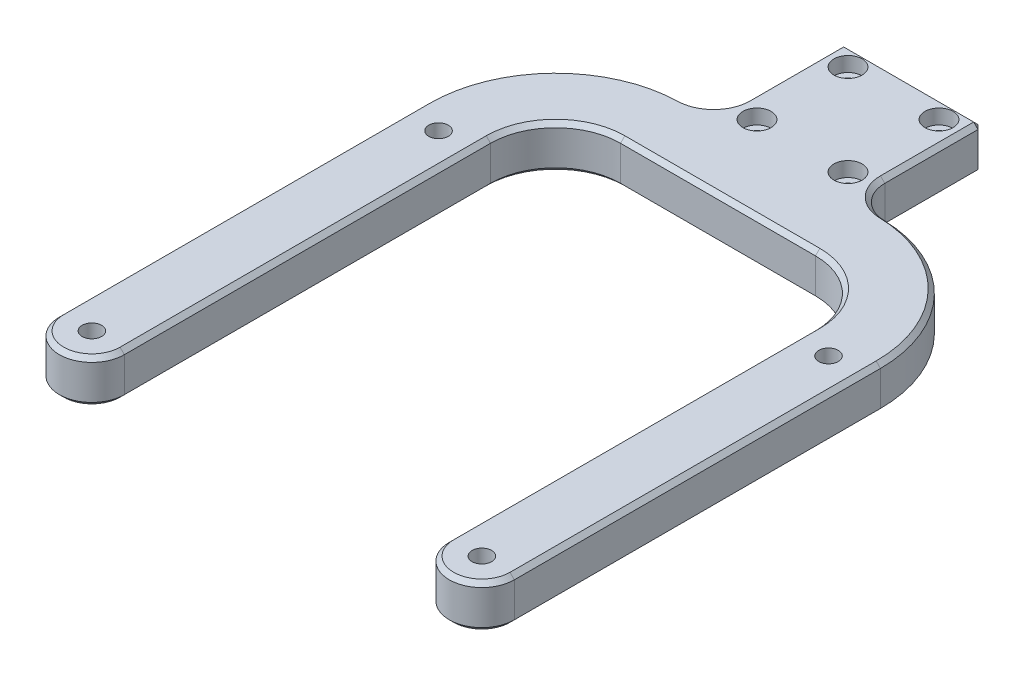
SolidWorks part; units mm, degrees
material "ABS PC"
ref_plane "Front Plane" through (0, 0, 0) normal (0, 0, 1) x (1, 0, 0)
ref_plane "Top Plane" through (0, 0, 0) normal (0, 1, 0) x (1, 0, 0)
ref_plane "Right Plane" through (0, 0, 0) normal (1, 0, 0) x (0, 0, -1)
sketch "Sketch1" plane through (0, 0, 0) normal (0, 1, 0) x (1, 0, 0)
  line L0 (22.5, 57.25) -> (0, 57.25)
  line L1 (0, 57.25) -> (0, 102.25)
  line L2 (37.5, 42.25) -> (37.5, -42.25)
  line L7 (16, 102.25) -> (0, 102.25)
  line L8 (0, 0) -> (0, 57.25) construction
  line L9 (16, 102.25) -> (16, 72.25)
  line L13 (16, 72.25) -> (22.5, 72.25)
  line L14 (52.5, 42.25) -> (52.5, -42.25)
  arc A4 (22.5, 57.25) -> (37.5, 42.25) centre (22.5, 42.25) cw
  arc A6 (22.5, 72.25) -> (52.5, 42.25) centre (22.5, 42.25) cw
  arc A9 (37.5, -42.25) -> (52.5, -42.25) centre (45, -42.25) ccw
  circle A10 centre (45, 37.75) radius 2.25
  circle A11 centre (45, -42.25) radius 2.25
  point P10 (37.5, 0)
  dimension "D7" = 80
  dimension "D8" = 30
  dimension "D9" = 15
  dimension "D6" = 107
  dimension "D14" = 4.5
  dimension "D1" = 15
  dimension "D2" = 15
  dimension "D3" = 30
  dimension "D4" = 32
  dimension "D5" = 75
extrude "Boss-Extrude1" add sketch "Sketch1" along normal blind 10
fillet "Fillet1" radius 7.5 1 edges at (16, 5, -72.25)
chamfer "Chamfer1" distance 1 angle 45 19 edges at (11.25, 0, -57.25) (33.1066, 0, -52.8566) (37.5, 0, 0) (52.5, 0, 0) (43.9942, 0, -63.1784) (16, 0, -90.9933) (8, 0, -102.25) (11.25, 10, -57.25) (33.1066, 10, -52.8566) (37.5, 10, 0) (52.5, 10, 0) (43.9942, 10, -63.1784) (16, 10, -90.9933) (8, 10, -102.25) (18.1265, 0, -74.5046) (18.1265, 10, -74.5046) (16, 5, -102.25) (45, 0, 49.75) (45, 10, 49.75)
sketch "Sketch5" plane through (0, 0, 0) normal (0, -1, 0) x (1, 0, 0)
  circle A0 centre (45, -37.75) radius 2.25 construction
  circle A1 centre (45, 42.25) radius 2.25 construction
  circle A2 centre (45, -37.75) radius 2.25
  circle A3 centre (45, 42.25) radius 2.25
extrude "Boss-Extrude2" add sketch "Sketch5" against normal offset from surface (4 mm away) 6 up to face at (26.3251, 10, -47.0845)
mirror "Mirror1" about plane through (0, 10, -57.25) normal (1, 0, 0) of bodies 104 101
sketch "Sketch6" plane through (0, 10, 0) normal (0, 1, 0) x (1, 0, 0)
  line L0 (-15, 102.25) -> (15, 102.25) construction
  line L1 (-16, 102.25) -> (16, 102.25) construction
  line L2 (-16, 102.25) -> (-16, 72.25) construction
  line L3 (-16, 72.25) -> (16, 72.25) construction
  line L4 (16, 102.25) -> (16, 72.25) construction
  line L5 (16, 101.25) -> (16, 79.7367) construction
  line L7 (-10.5, 97.75) -> (10.5, 97.75) construction
  line L8 (-10.5, 97.75) -> (-10.5, 76.75) construction
  line L9 (-10.5, 76.75) -> (10.5, 76.75) construction
  line L10 (10.5, 97.75) -> (10.5, 76.75) construction
  circle A0 centre (10.5, 97.75) radius 1.5 construction
  circle A1 centre (10.5, 76.75) radius 1.5 construction
  circle A2 centre (-10.5, 97.75) radius 1.5 construction
  circle A3 centre (-10.5, 76.75) radius 1.5 construction
  dimension "D3" = 3
  dimension "D4" = 18
  dimension "D5" = 3
  dimension "D6" = 4
  dimension "D7" = 18
  dimension "D1" = 32
  dimension "D2" = 30
hole_wizard "CBORE for M3 Hex Socket Head Cap Screw1" positions "Sketch7" profile "Sketch8" counterbore size "M3" standard "ISO" end condition through all
sketch "Sketch7" plane through (0, 10, 0) normal (0, 1, 0) x (1, 0, 0)
  point P0 (10.5, 97.75)
  point P3 (-10.5, 97.75)
  point P6 (-10.5, 76.75)
  point P9 (10.5, 76.75)
sketch "Sketch8" plane through (10.5, 10, -97.75) normal (1, 0, 0) x (0, 0, 1)
  line L0 (0, 0) -> (0, 10)
  line L1 (0, 10) -> (1.7, 10)
  line L3 (1.7, 10) -> (1.7, 3.4)
  line L4 (1.7, 3.4) -> (3.25, 3.4)
  line L5 (3.25, 3.4) -> (3.25, 0)
  line L7 (3.25, 0) -> (0, 0)
  line L11 (0, -6.35) -> (0, 107.95) construction
  dimension "Thru Hole Dia." = 3.4
  dimension "Thru Hole Depth" = 10
  dimension "C'Bore Dia." = 6.5
  dimension "C'Bore Depth" = 3.4
